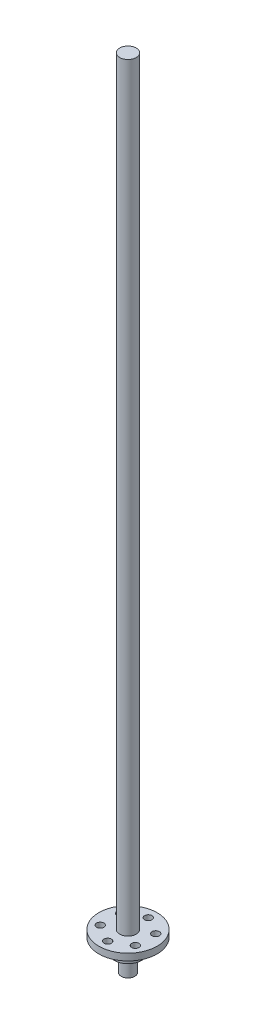
SolidWorks part; units mm, degrees
material "Cast Alloy Steel"
ref_plane "Front Plane" through (0, 0, 0) normal (0, 0, 1) x (1, 0, 0)
ref_plane "Top Plane" through (0, 0, 0) normal (0, 1, 0) x (1, 0, 0)
ref_plane "Right Plane" through (0, 0, 0) normal (1, 0, 0) x (0, 0, -1)
sketch "Sketch1" plane through (0, 0, 0) normal (0, 1, 0) x (1, 0, 0)
  circle A0 centre (0, 0) radius 26.845
extrude "Boss-Extrude1" add sketch "Sketch1" along normal blind 6.23
sketch "Sketch2" plane through (0, 6.23, 0) normal (0, 1, 0) x (1, 0, 0)
  circle A0 centre (0, 0) radius 7.625
extrude "Boss-Extrude2" add sketch "Sketch2" along normal blind 700
sketch "Sketch3" plane through (0, 0, 0) normal (0, -1, 0) x (1, 0, 0)
  circle A0 centre (0, 0) radius 12.91
extrude "Boss-Extrude3" add sketch "Sketch3" along normal blind 12
sketch "Sketch4" plane through (0, 0, 0) normal (0, -1, 0) x (-1, 0, 0)
  circle A0 centre (0, 18.7182) radius 3.3946
extrude "Cut-Extrude1" cut sketch "Sketch4" against normal blind 12
ref_axis "Axis1" through (0, -12, 0) along (0, 1, 0)
pattern_circular "CirPattern1" count 6 every 60 about axis through (0, -12, 0) along (0, 1, 0) of "Cut-Extrude1"
sketch "Sketch6" plane through (0, -12, 0) normal (0, -1, 0) x (-1, 0, 0)
  circle A0 centre (0, 0) radius 6.26
extrude "Boss-Extrude4" add sketch "Sketch6" along normal blind 16.13
